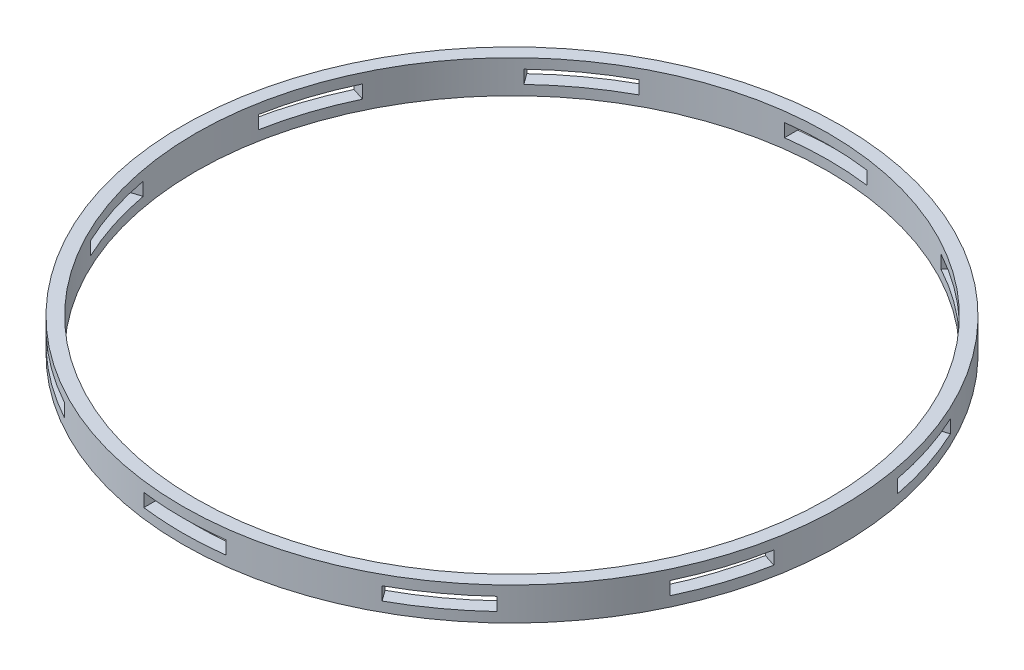
SolidWorks part; units mm, degrees
ref_plane "Front Plane" through (0, 0, 0) normal (0, 0, 1) x (1, 0, 0)
ref_plane "Top Plane" through (0, 0, 0) normal (0, 1, 0) x (1, 0, 0)
ref_plane "Right Plane" through (0, 0, 0) normal (1, 0, 0) x (0, 0, -1)
sketch "Sketch1" plane through (0, 0, 0) normal (0, 1, 0) x (1, 0, 0)
  line L0 (40.8443, 86.8778) -> (42.5461, 90.4977) construction
  circle A0 centre (0, 0) radius 96
  circle A1 centre (0, 0) radius 100
  dimension "D2" = 192
  dimension "D1" = 4
extrude "Boss-Extrude1" add sketch "Sketch1" along normal blind 10
sketch "Sketch2" plane through (0, 0, 0) normal (0, 0, 1) x (1, 0, 0)
  line L0 (-100, 0) -> (100, 0) construction
  line L1 (-12.5, 7) -> (12.5, 7)
  line L2 (-12.5, 7) -> (-12.5, 3)
  line L3 (-12.5, 3) -> (12.5, 3)
  line L4 (12.5, 7) -> (12.5, 3)
  line L5 (96, 10) -> (-96, 10) construction
  point P11 (0, 3)
  dimension "D1" = 3
  dimension "D2" = 3
  dimension "D3" = 25
extrude "Cut-Extrude1" cut sketch "Sketch2" against normal through all
ref_axis "Axis1" through (0, 10, 0) along (0, -1, 0)
pattern_circular "CirPattern1" count 10 over 360 about axis through (0, 10, 0) along (0, -1, 0) of "Cut-Extrude1"
